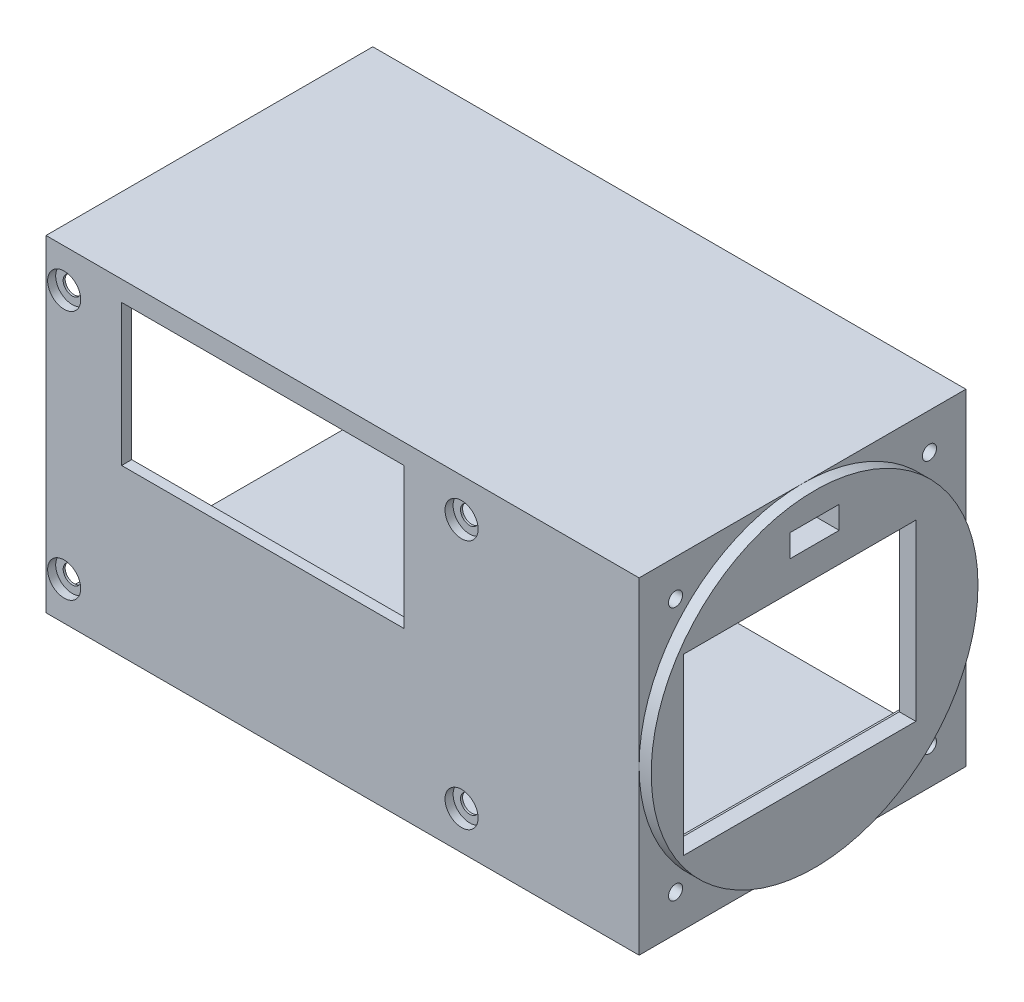
SolidWorks part; units mm, degrees
ref_plane "Płaszczyzna przednia" through (0, 0, 0) normal (0, 0, 1) x (1, 0, 0)
ref_plane "Płaszczyzna górna" through (0, 0, 0) normal (0, 1, 0) x (1, 0, 0)
ref_plane "Płaszczyzna prawa" through (0, 0, 0) normal (1, 0, 0) x (0, 0, -1)
sketch "Szkic1" plane through (0, 0, 0) normal (1, 0, 0) x (0, 0, -1)
  line L0 (0, 81) -> (81, 81)
  line L1 (81, 81) -> (81, 0)
  line L2 (81, 0) -> (0, 0)
  line L3 (0, 0) -> (0, 81)
  line L4 (8, 62.1) -> (65.6, 62.1)
  line L5 (65.6, 62.1) -> (65.6, 18.9)
  line L6 (65.6, 18.9) -> (8, 18.9)
  line L7 (8, 18.9) -> (8, 62.1)
  line L8 (3, 68.16) -> (76.3, 68.16) construction
  line L9 (76.3, 68.16) -> (76.3, 12.84) construction
  line L10 (76.3, 12.84) -> (3, 12.84) construction
  line L11 (3, 12.84) -> (3, 68.16) construction
  circle A0 centre (40.5, 40.5) radius 40.5
  point P15 (0, 40.5)
  point P16 (8, 40.5)
  dimension "D1" = 81
  dimension "D2" = 57.6
  dimension "D3" = 43.2
  dimension "D4" = 73.3
  dimension "D5" = 55.32
  dimension "D6" = 6.06
  dimension "D7" = 5
  dimension "D8" = 3
extrude "Dodanie-wyciągnięcie1" add sketch "Szkic1" along normal blind 8 contours A0 L6 L7 L4 L5 region at (0, 68.3278, -68.3278)
extrude "Dodanie-wyciągnięcie2" add sketch "Szkic1<3>" along normal blind 5 contours A0 L0 L3 | A0 L1 L0 | A0 L2 L1 | A0 L3 L2 region at (0, 71.9536, -9.0464) region at (0, 71.9536, -71.9536) region at (0, 9.0464, -9.0464) region at (0, 9.0464, -71.9536)
sketch "Szkic1<3>" plane through (0, 0, 0) normal (1, 0, 0) x (0, 0, -1) same geometry as "Szkic1"
sketch "Szkic2" plane through (0, 0, 0) normal (-1, 0, 0) x (0, 0, 1)
  line L0 (-74.26, 65.56) -> (-4.94, 65.56)
  line L1 (-4.94, 65.56) -> (-4.94, 15.44)
  line L2 (-4.94, 15.44) -> (-74.26, 15.44)
  line L3 (-74.26, 15.44) -> (-74.26, 65.56)
  line L4 (-76.3, 68.16) -> (-3, 68.16)
  line L5 (-3, 68.16) -> (-3, 12.84)
  line L6 (-3, 12.84) -> (-76.3, 12.84)
  line L7 (-76.3, 12.84) -> (-76.3, 68.16)
  line L8 (0, 0) -> (0, 81) construction
  line L9 (0, 81) -> (-81, 81) construction
  line L10 (-81, 81) -> (-81, 0) construction
  line L11 (-81, 0) -> (0, 0) construction
  line L12 (0, 0) -> (0, 81)
  line L13 (0, 81) -> (-81, 81)
  line L14 (-81, 81) -> (-81, 0)
  line L15 (-81, 0) -> (0, 0)
  point P9 (-3, 40.5)
  line M3 (-8, 18.9) -> (-65.6, 18.9)
  line M4 (-65.6, 18.9) -> (-65.6, 62.1)
  line M5 (-65.6, 62.1) -> (-8, 62.1)
  line M6 (-8, 62.1) -> (-8, 18.9)
  line M7 (-81, 0) -> (0, 0)
  line M8 (0, 0) -> (0, 81)
  line M9 (0, 81) -> (-81, 81)
  line M10 (-81, 81) -> (-81, 0)
  dimension "D1" = 69.32
  dimension "D2" = 50.12
  dimension "D3" = 73.3
  dimension "D4" = 55.32
  dimension "D5" = 1.94
  dimension "D6" = 2.6
  dimension "D7" = 3
extrude "Wytnij-wyciągnięcie1" cut sketch "Szkic2" against normal blind 3.9 contours L3 L2 L1 L0 M6 M3 M4 M5 region at (0, 64.7046, -39.6)
extrude "Dodanie-wyciągnięcie3" add sketch "Szkic2<4>" along normal blind 2 contours L6 L7 L4 L5 M10 M7 M8 M9 region at (0, 1.1455, -40.5)
sketch "Szkic2<4>" plane through (0, 0, 0) normal (-1, 0, 0) x (0, 0, 1) same geometry as "Szkic2"
sketch "Szkic3" plane through (-2, 0, 0) normal (-1, 0, 0) x (0, 0, 1)
  line L0 (-81, 0) -> (0, 0) construction
  line L1 (0, 0) -> (0, 81) construction
  line L2 (0, 81) -> (-81, 81) construction
  line L3 (-81, 0) -> (0, 0)
  line L4 (0, 0) -> (0, 81)
  line L5 (0, 81) -> (-81, 81)
  line L6 (-81, 3) -> (-3, 3)
  line L7 (-3, 3) -> (-3, 78)
  line L8 (-3, 78) -> (-81, 78)
  line L9 (-81, 81) -> (-81, 78)
  line L10 (-81, 3) -> (-81, 0)
  dimension "D1" = 3
extrude "Dodanie-wyciągnięcie4" add sketch "Szkic3" along normal blind 140
sketch "Szkic5" plane through (0, 0, 0) normal (0, 0, 1) x (1, 0, 0)
  line L0 (-137.5, 9.5) -> (-137.5, 71.5) construction
  line L1 (-137.5, 71.5) -> (-39, 71.5) construction
  line L2 (-39, 71.5) -> (-39, 9.5) construction
  line L3 (-39, 9.5) -> (-137.5, 9.5) construction
  line L6 (-142, 76) -> (5, 76) construction
  line L7 (-142, 0) -> (-142, 81) construction
  line L8 (5, 40.5) -> (5, 81) construction
  line L9 (-142, 5) -> (5, 5) construction
  line L10 (5, 0) -> (5, 40.5) construction
  line L11 (5, 81) -> (-142, 81) construction
  line L12 (5, 0) -> (-142, 0) construction
  circle A0 centre (-137.5, 71.5) radius 2.25
  circle A1 centre (-39, 71.5) radius 2.25
  circle A2 centre (-137.5, 9.5) radius 2.25
  circle A3 centre (-39, 9.5) radius 2.25
  circle A4 centre (-137.5, 71.5) radius 4.5 construction
  dimension "D3" = 4.5
  dimension "D4" = 9
  dimension "D1" = 98.5
  dimension "D2" = 62
  dimension "D5" = 5
  dimension "D6" = 5
extrude "Wytnij-wyciągnięcie2" cut sketch "Szkic5" against normal up to next
sketch "Szkic6" plane through (0, 0, 0) normal (0, 0, 1) x (1, 0, 0)
  circle A0 centre (-137.5, 71.5) radius 4.1
  circle A1 centre (-137.5, 71.5) radius 2.25 construction
  circle A2 centre (-39, 71.5) radius 4.1
  circle A3 centre (-39, 9.5) radius 4.1
  circle A4 centre (-137.5, 9.5) radius 4.1
  circle A5 centre (-39, 71.5) radius 2.25 construction
  circle A6 centre (-137.5, 9.5) radius 2.25 construction
  circle A7 centre (-39, 9.5) radius 2.25 construction
  dimension "D1" = 8.2
extrude "Wytnij-wyciągnięcie3" cut sketch "Szkic6" against normal blind 2
sketch "Szkic7" plane through (0, 0, 0) normal (0, 0, 1) x (1, 0, 0)
  line L1 (-53.25, 76) -> (-53.25, 41)
  line L2 (-53.25, 41) -> (-123.25, 41)
  line L3 (-123.25, 41) -> (-123.25, 76)
  line L4 (5, 81) -> (-142, 81) construction
  line L5 (-137.5, 71.5) -> (-39, 71.5) construction
  line L11 (-53.25, 76) -> (-123.25, 76)
  point P2 (-88.25, 71.5)
  point P11 (-88.25, 76)
  dimension "D1" = 70
  dimension "D2" = 35
  dimension "D3" = 5
extrude "Wytnij-wyciągnięcie4" cut sketch "Szkic7" against normal up to next
sketch "Szkic8" plane through (5, 0, 0) normal (1, 0, 0) x (0, 0, -1)
  line L0 (-4, 40.5) -> (85, 40.5) construction
  line L1 (9.0337, 71.9663) -> (71.9663, 9.0337) construction
  line L2 (9.0337, 9.0337) -> (71.9663, 71.9663) construction
  circle A0 centre (40.5, 40.5) radius 44.5 construction
  circle A1 centre (40.5, 40.5) radius 40.5 construction
  circle A2 centre (9.0337, 71.9663) radius 1.75
  circle A3 centre (71.9663, 71.9663) radius 1.75
  circle A4 centre (71.9663, 9.0337) radius 1.75
  circle A5 centre (9.0337, 9.0337) radius 1.75
  dimension "D1" = 89
  dimension "D3" = 3.5
  dimension "D2" = 45
extrude "Wytnij-wyciągnięcie5" cut sketch "Szkic8" against normal up to next
sketch "Szkic9" plane through (8, 0, 0) normal (1, 0, 0) x (0, 0, -1)
  line L0 (34.4, 75) -> (34.4, 69.4)
  line L1 (34.4, 69.4) -> (46.6, 69.4)
  line L2 (46.6, 69.4) -> (46.6, 75)
  line L3 (46.6, 75) -> (34.4, 75)
  line L4 (40.5, 0) -> (40.5, 81) construction
  circle A0 centre (40.5, 40.5) radius 40.5 construction
  point P12 (40.5, 69.4)
  dimension "D1" = 12.2
  dimension "D2" = 5.6
  dimension "D3" = 6
extrude "Wytnij-wyciągnięcie6" cut sketch "Szkic9" against normal up to next
sketch "Szkic10" plane through (0, 78, 0) normal (0, -1, 0) x (1, 0, 0)
  line L4 (-2, -81) -> (-2, -3)
  line L5 (-2, -3) -> (-142, -3)
  line L6 (-142, -3) -> (-142, -81)
  line L7 (-142, -81) -> (-2, -81)
  line L8 (-2, -81) -> (-2, -3)
  line L9 (-2, -3) -> (-142, -3)
  line L10 (-142, -3) -> (-142, -81)
  line L11 (-142, -81) -> (-2, -81)
  dimension "D1" = 0
extrude "Wytnij-wyciągnięcie7" cut sketch "Szkic10" against normal blind 0.5
sketch "Szkic11" plane through (0, 3, 0) normal (0, 1, 0) x (1, 0, 0)
  line L4 (-2, 3) -> (-2, 81)
  line L5 (-2, 81) -> (-142, 81)
  line L6 (-142, 81) -> (-142, 3)
  line L7 (-142, 3) -> (-2, 3)
  line L8 (-2, 3) -> (-2, 81)
  line L9 (-2, 81) -> (-142, 81)
  line L10 (-142, 81) -> (-142, 3)
  line L11 (-142, 3) -> (-2, 3)
  dimension "D1" = 0
extrude "Wytnij-wyciągnięcie8" cut sketch "Szkic11" against normal blind 0.5
sketch "Szkic12" plane through (-2, 0, 0) normal (-1, 0, 0) x (0, 0, 1)
  line L8 (-81, 78.5) -> (-81, 2.5)
  line L9 (-81, 2.5) -> (-3, 2.5)
  line L10 (-3, 2.5) -> (-3, 12.84)
  line L11 (-3, 12.84) -> (-76.3, 12.84)
  line L12 (-76.3, 12.84) -> (-76.3, 68.16)
  line L13 (-76.3, 68.16) -> (-3, 68.16)
  line L14 (-3, 68.16) -> (-3, 78.5)
  line L15 (-3, 78.5) -> (-81, 78.5)
  line L16 (-81, 78.5) -> (-81, 2.5)
  line L17 (-81, 2.5) -> (-3, 2.5)
  line L18 (-3, 2.5) -> (-3, 12.84)
  line L19 (-3, 12.84) -> (-76.3, 12.84)
  line L20 (-76.3, 12.84) -> (-76.3, 68.16)
  line L21 (-76.3, 68.16) -> (-3, 68.16)
  line L22 (-3, 68.16) -> (-3, 78.5)
  line L23 (-3, 78.5) -> (-81, 78.5)
  dimension "D1" = 0
extrude "Wytnij-wyciągnięcie9" cut sketch "Szkic12" against normal blind 0.5
sketch "Szkic13" plane through (0, 0, -3) normal (0, 0, -1) x (-1, 0, 0)
  line L8 (1.5, 78.5) -> (1.5, 68.16)
  line L9 (1.5, 68.16) -> (0, 68.16)
  line L10 (0, 68.16) -> (0, 12.84)
  line L11 (0, 12.84) -> (1.5, 12.84)
  line L12 (1.5, 12.84) -> (1.5, 2.5)
  line L13 (1.5, 2.5) -> (142, 2.5)
  line L14 (142, 2.5) -> (142, 78.5)
  line L15 (142, 78.5) -> (1.5, 78.5)
  line L16 (1.5, 78.5) -> (1.5, 68.16)
  line L17 (1.5, 68.16) -> (0, 68.16)
  line L18 (0, 68.16) -> (0, 12.84)
  line L19 (0, 12.84) -> (1.5, 12.84)
  line L20 (1.5, 12.84) -> (1.5, 2.5)
  line L21 (1.5, 2.5) -> (142, 2.5)
  line L22 (142, 2.5) -> (142, 78.5)
  line L23 (142, 78.5) -> (1.5, 78.5)
  dimension "D1" = 0
extrude "Wytnij-wyciągnięcie10" cut sketch "Szkic13" against normal blind 0.5
equation "\"D3@Szkic8\"= 3.5"
